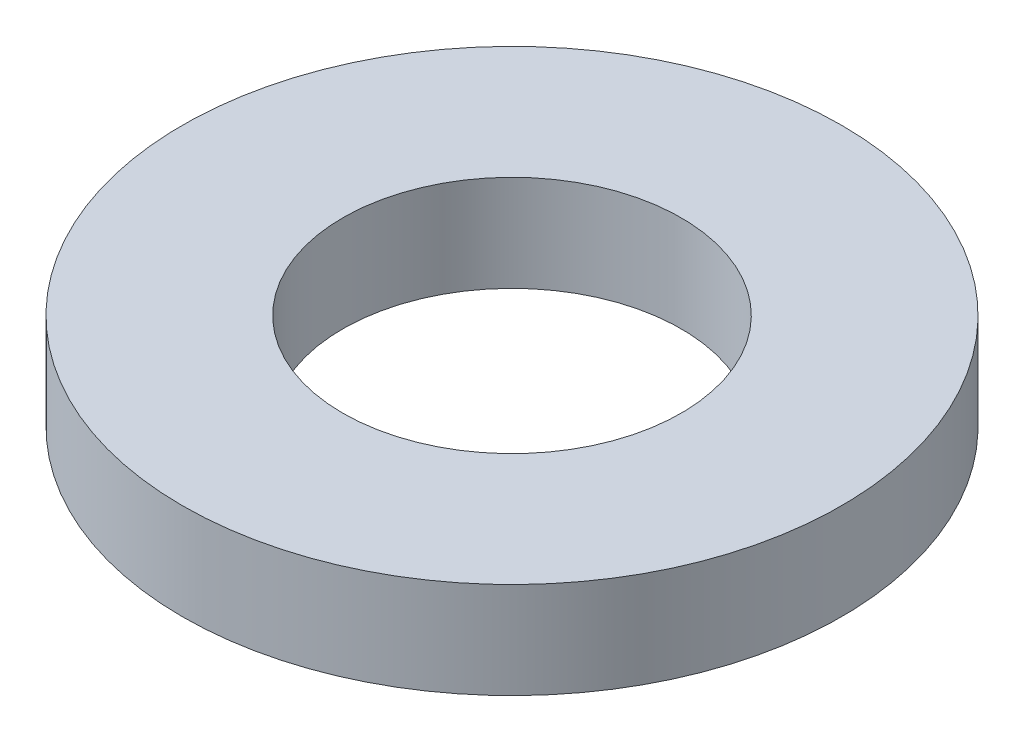
SolidWorks part; units mm, degrees
ref_plane "Front Plane" through (0, 0, 0) normal (0, 0, 1) x (1, 0, 0)
ref_plane "Top Plane" through (0, 0, 0) normal (0, 1, 0) x (1, 0, 0)
ref_plane "Right Plane" through (0, 0, 0) normal (1, 0, 0) x (0, 0, -1)
sketch "Sketch1" plane through (0, 0, 0) normal (0, 1, 0) x (1, 0, 0)
  circle A0 centre (0, 0) radius 92.5
  dimension "FLANGE_OD" = 185
extrude "Boss-Extrude1" add sketch "Sketch1" along normal blind 27
sketch "Sketch2" plane through (0, 0, 0) normal (0, 1, 0) x (1, 0, 0)
  circle A0 centre (0, 0) radius 47.5
  dimension "BORE_D" = 95
extrude "Cut-Extrude1" cut sketch "Sketch2" along normal through all
sketch "Sketch3" plane through (0, 27, 0) normal (0, 1, 0) x (1, 0, 0)
  circle A0 centre (0, 0) radius 29.0932 construction
  circle A1 centre (-29.0932, 0) radius 1.561
  dimension "BOLT_D" = 3.1221
  dimension "BOLT_PCD" = 58.1863
extrude "Cut-Extrude2" cut sketch "Sketch3" against normal blind 16.2155 rebuild error yes
pattern_circular "CirPattern1" count 5 over 360 rebuild error yes
